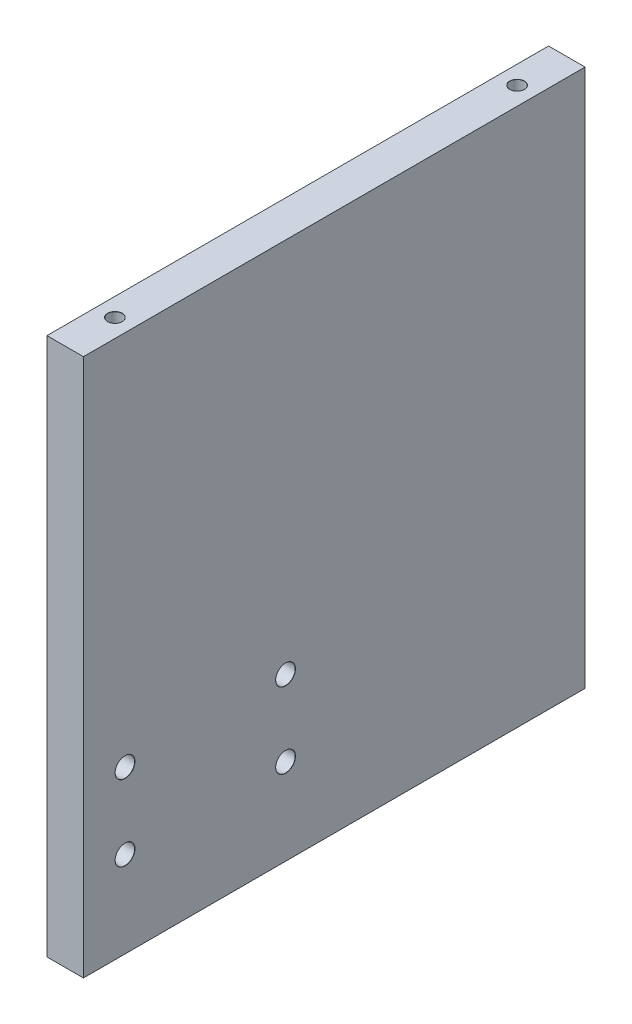
SolidWorks part; units mm, degrees
ref_plane "Front Plane" through (0, 0, 0) normal (0, 0, 1) x (1, 0, 0)
ref_plane "Top Plane" through (0, 0, 0) normal (0, 1, 0) x (1, 0, 0)
ref_plane "Right Plane" through (0, 0, 0) normal (1, 0, 0) x (0, 0, -1)
sketch "Sketch1" plane through (0, 0, 0) normal (1, 0, 0) x (0, 0, -1)
  line L1 (-43.65, -46.825) -> (43.65, -46.825)
  line L2 (-43.65, -46.825) -> (-43.65, 46.825)
  line L3 (-43.65, 46.825) -> (43.65, 46.825)
  line L4 (43.65, -46.825) -> (43.65, 46.825)
  line L5 (-43.65, -46.825) -> (43.65, 46.825) construction
  line L6 (-43.65, 46.825) -> (43.65, -46.825) construction
  point P0 (0, 0)
extrude "Boss-Extrude1" add sketch "Sketch1" along normal blind 6.35
sketch "Sketch2" plane through (0, 46.825, 0) normal (0, 1, 0) x (1, 0, 0)
  line L0 (3.175, 43.65) -> (3.175, 35)
  line L1 (6.35, 43.65) -> (0, 43.65) construction
  line L2 (3.175, -43.65) -> (3.175, -35)
  line L3 (6.35, -43.65) -> (0, -43.65) construction
hole_wizard "Tap Drill for M3x0.5 Tap1" positions "Sketch3" profile "Sketch4" hole size "M3x0.5" standard "ANSI Metric"
sketch "Sketch3" plane through (0, 46.825, 0) normal (0, 1, 0) x (1, 0, 0)
  point P0 (3.175, 35)
  point P3 (3.175, -35)
sketch "Sketch4" plane through (3.175, 46.825, -35) normal (1, 0, 0) x (0, 0, 1)
  line L0 (0, 0) -> (0, 10.7511)
  line L1 (0, 10.7511) -> (1.25, 10)
  line L2 (1.25, 10) -> (1.25, 0.025)
  line L3 (1.25, 0.025) -> (1.275, 0)
  line L5 (1.275, 0) -> (0, 0)
  line L6 (-1.25, 0.025) -> (-1.275, 0) construction
  line L10 (0, 10.7511) -> (-1.25, 10) construction
  line L11 (0, -6.35) -> (0, 107.95) construction
  dimension "Hole Dia." = 2.5
  dimension "Hole Depth" = 10
  dimension "Near C'Sink Dia." = 2.55
  dimension "Near C'Sink Angle" = 90
  dimension "Drill Angle" = 118
sketch "Sketch5" plane through (0, -46.825, 0) normal (0, -1, 0) x (1, 0, 0)
  line L0 (3.175, 43.65) -> (3.175, 35)
  line L1 (3.175, -43.65) -> (3.175, -35)
  line L2 (6.35, -43.65) -> (0, -43.65) construction
hole_wizard "Tap Drill for M3x0.5 Tap2" positions "Sketch6" profile "Sketch7" hole size "M3x0.5" standard "ANSI Metric"
sketch "Sketch6" plane through (0, -46.825, 0) normal (0, -1, 0) x (-1, 0, 0)
  point P0 (-3.175, -35)
  point P3 (-3.175, 35)
sketch "Sketch7" plane through (3.175, -46.825, 35) normal (1, 0, 0) x (0, 0, -1)
  line L0 (0, 0) -> (0, 10)
  line L1 (0, 10) -> (1.25, 9.2489)
  line L2 (1.25, 9.2489) -> (1.25, 0.025)
  line L3 (1.25, 0.025) -> (1.275, 0)
  line L5 (1.275, 0) -> (0, 0)
  line L6 (-1.25, 0.025) -> (-1.275, 0) construction
  line L10 (0, 10) -> (-1.25, 9.2489) construction
  line L11 (0, -6.35) -> (0, 107.95) construction
  dimension "Hole Dia." = 2.5
  dimension "Hole Depth" = 10
  dimension "Near C'Sink Dia." = 2.55
  dimension "Near C'Sink Angle" = 90
  dimension "Drill Angle" = 118
sketch "Sketch8" plane through (6.35, 0, 0) normal (1, 0, 0) x (0, 0, -1)
  line L0 (-43.65, -46.825) -> (-43.65, -31.825)
  line L1 (-43.65, 46.825) -> (-43.65, -46.825) construction
  line L2 (-43.65, -31.825) -> (-36.41, -31.825)
  line L3 (-36.41, -31.825) -> (-8.47, -31.825)
  line L4 (-36.41, -31.825) -> (-36.41, -18.655)
  line L5 (-8.47, -31.825) -> (-8.47, -18.655)
hole_wizard "M3 Clearance Hole1" positions "Sketch9" profile "Sketch10" hole size "M3" standard "ANSI Metric" end condition through all
sketch "Sketch9" plane through (6.35, 0, 0) normal (1, 0, 0) x (0, 0, -1)
  point P0 (-36.41, -18.655)
  point P3 (-8.47, -18.655)
  point P6 (-8.47, -31.825)
  point P9 (-36.41, -31.825)
sketch "Sketch10" plane through (6.35, -18.655, 36.41) normal (0, 1, 0) x (0, 0, -1)
  line L0 (0, 0) -> (0, 6.35)
  line L1 (0, 6.35) -> (1.7, 6.35)
  line L2 (1.7, 6.35) -> (1.7, 0.025)
  line L3 (1.7, 0.025) -> (1.725, 0)
  line L5 (1.725, 0) -> (0, 0)
  line L6 (-1.7, 0.025) -> (-1.725, 0) construction
  line L11 (0, -6.35) -> (0, 107.95) construction
  dimension "Thru Hole Dia." = 3.4
  dimension "Thru Hole Depth" = 6.35
  dimension "Near C'Sink Dia." = 3.45
  dimension "Near C'Sink Angle" = 90
